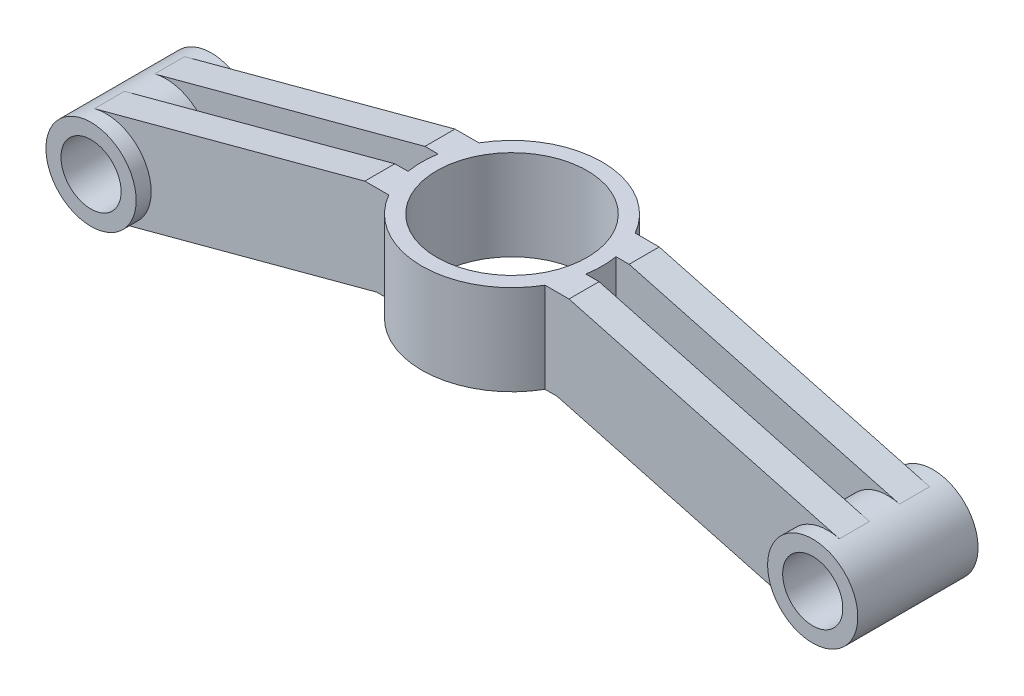
SolidWorks part; units mm, degrees
ref_plane "Front Plane" through (0, 0, 0) normal (0, 0, 1) x (1, 0, 0)
ref_plane "Top Plane" through (0, 0, 0) normal (0, 1, 0) x (1, 0, 0)
ref_plane "Right Plane" through (0, 0, 0) normal (1, 0, 0) x (0, 0, -1)
sketch "Sketch1" plane through (0, 0, 0) normal (0, 0, 1) x (1, 0, 0)
  line L0 (0, 0) -> (-120, 0) construction
  line L1 (0, 8.5863) -> (-30, 8.5863)
  line L2 (-30, 8.5863) -> (-116.1177, -14.4889)
  line L3 (0, 38.5863) -> (-33.9496, 38.5863)
  line L4 (-33.9496, 38.5863) -> (-123.8823, 14.4889)
  line L5 (0, 38.5863) -> (0, 8.5863)
  circle A0 centre (-120, 0) radius 10
  circle A1 centre (-120, 0) radius 15
  dimension "D2" = 30
  dimension "D3" = 20
  dimension "D1" = 120
  dimension "D4" = 165
  dimension "D5" = 30
  dimension "D6" = 30
extrude "Boss-Extrude1" add sketch "Sketch1" against normal blind 40 contours A1 A0 region at (-134.0791, -3.7725, 0)
sketch "Sketch2" plane through (0, 0, 0) normal (0, 0, 1) x (1, 0, 0)
  line L0 (0, 38.5863) -> (0, 8.5863) construction
  line L1 (0, 8.5863) -> (-30, 8.5863) construction
  line L2 (0, 38.5863) -> (-33.9496, 38.5863) construction
  line L3 (-33.9496, 38.5863) -> (-123.8823, 14.4889) construction
  line L4 (-30, 8.5863) -> (-116.1177, -14.4889) construction
  line L5 (0, 38.5863) -> (0, 8.5863)
  line L6 (0, 8.5863) -> (-30, 8.5863)
  line L7 (0, 38.5863) -> (-33.9496, 38.5863)
  line L8 (-33.9496, 38.5863) -> (-123.8823, 14.4889)
  line L9 (-30, 8.5863) -> (-116.1177, -14.4889)
  circle A0 centre (-120, 0) radius 15 construction
  arc A1 (-116.1177, -14.4889) -> (-123.8823, 14.4889) centre (-120, 0) ccw
extrude "Boss-Extrude2" add sketch "Sketch2" against normal blind 10 from offset 5 offset against normal yes
sketch "Sketch3" plane through (0, 0, 0) normal (0, 0, 1) x (1, 0, 0)
  line L0 (-116.1177, -14.4889) -> (-30, 8.5863) construction
  line L1 (-30, 8.5863) -> (0, 8.5863) construction
  line L2 (0, 8.5863) -> (0, 38.5863) construction
  line L3 (0, 38.5863) -> (-33.9496, 38.5863) construction
  line L4 (-33.9496, 38.5863) -> (-123.8823, 14.4889) construction
  line L5 (-116.1177, -14.4889) -> (-30, 8.5863)
  line L6 (-30, 8.5863) -> (0, 8.5863)
  line L7 (0, 8.5863) -> (0, 38.5863)
  line L8 (0, 38.5863) -> (-33.9496, 38.5863)
  line L9 (-33.9496, 38.5863) -> (-123.8823, 14.4889)
  circle A0 centre (-120, 0) radius 15 construction
  arc A1 (-116.1177, -14.4889) -> (-123.8823, 14.4889) centre (-120, 0) ccw
extrude "Boss-Extrude3" add sketch "Sketch3" against normal blind 10 from offset 25 offset against normal yes
mirror "Mirror1" about plane through (0, 0, 0) normal (1, 0, 0) of bodies 103
sketch "Sketch4" plane through (0, 38.5863, 0) normal (0, 1, 0) x (1, 0, 0)
  line L0 (0, 35) -> (0, 5) construction
  line L1 (33.9496, 35) -> (-33.9496, 35) construction
  line L2 (33.9496, 5) -> (-33.9496, 5) construction
  circle A0 centre (0, 20) radius 30
  circle A1 centre (0, 20) radius 25
  dimension "D1" = 60
  dimension "D2" = 50
extrude "Boss-Extrude4" add sketch "Sketch4" against normal blind 30
sketch "Sketch5" plane through (0, 0, 0) normal (0, 1, 0) x (1, 0, 0)
  line L0 (0, 50) -> (0, -10) construction
  line L1 (-135, 20) -> (0, 20) construction
  line L2 (-135, 40) -> (-135, 0) construction
  circle A0 centre (0, 20) radius 25
  point P8 (0, 20)
  dimension "D2" = 50
  dimension "D1" = 60
extrude "Cut-Extrude3" cut sketch "Sketch5" along normal blind 50
